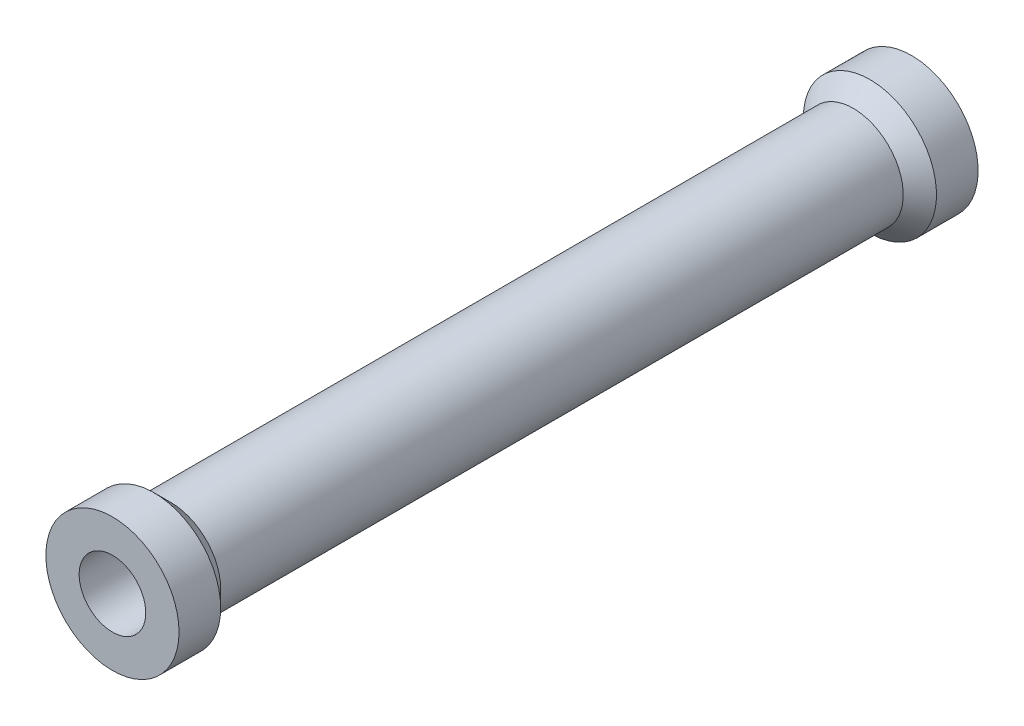
SolidWorks part; units mm, degrees
ref_plane "Front Plane" through (0, 0, 0) normal (0, 0, 1) x (1, 0, 0)
ref_plane "Top Plane" through (0, 0, 0) normal (0, 1, 0) x (1, 0, 0)
ref_plane "Right Plane" through (0, 0, 0) normal (1, 0, 0) x (0, 0, -1)
sketch "Sketch1" plane through (0, 0, 0) normal (0, 0, 1) x (1, 0, 0)
  circle A0 centre (0, 0) radius 4.7625
  dimension "D1" = 9.525
extrude "Boss-Extrude1" add sketch "Sketch1" along normal blind 31.75
sketch "Sketch2" plane through (0, 0, 31.75) normal (0, 0, 1) x (1, 0, 0)
  circle A0 centre (0, 0) radius 6.35
extrude "Boss-Extrude2" add sketch "Sketch2" along normal blind 6.35
chamfer "Chamfer1" distance 2.38 angle 45 1 edges at (6.35, 0, 31.75)
sketch "Sketch3" plane through (0, 0, 38.1) normal (0, 0, 1) x (1, 0, 0)
  circle A0 centre (0, 0) radius 3.175
extrude "Cut-Extrude1" cut sketch "Sketch3" against normal blind 12.7
sketch "Sketch4" plane through (0, 0, 0) normal (0, 0, -1) x (-1, 0, 0)
  circle A0 centre (0, 0) radius 4.7625
extrude "Boss-Extrude3" add sketch "Sketch4" along normal blind 31.75
sketch "Sketch5" plane through (0, 0, -31.75) normal (0, 0, -1) x (-1, 0, 0)
  circle A0 centre (0, 0) radius 6.35
extrude "Boss-Extrude4" add sketch "Sketch5" along normal blind 6.35
chamfer "Chamfer2" distance 2.38 angle 45 1 edges at (-6.35, 0, -31.75)
sketch "Sketch6" plane through (0, 0, -38.1) normal (0, 0, -1) x (-1, 0, 0)
  circle A0 centre (0, 0) radius 3.175
extrude "Cut-Extrude2" cut sketch "Sketch6" against normal blind 12.7
